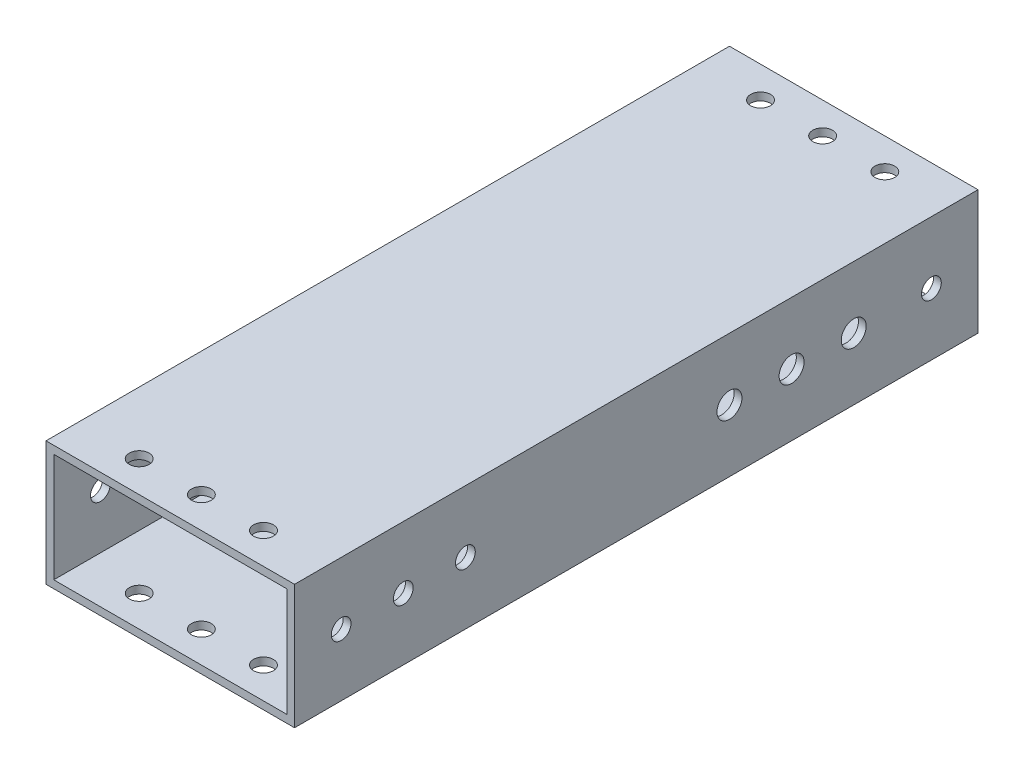
SolidWorks part; units mm, degrees
material "6061-T6 (SS)"
ref_plane "Front Plane" through (0, 0, 0) normal (0, 0, 1) x (1, 0, 0)
ref_plane "Top Plane" through (0, 0, 0) normal (0, 1, 0) x (1, 0, 0)
ref_plane "Right Plane" through (0, 0, 0) normal (1, 0, 0) x (0, 0, -1)
sketch "Sketch1" plane through (0, 0, 0) normal (0, 0, 1) x (1, 0, 0)
  line L0 (-23.8125, 11.1125) -> (23.8125, 11.1125)
  line L1 (-25.4, -12.7) -> (25.4, -12.7)
  line L2 (-25.4, -12.7) -> (-25.4, 12.7)
  line L3 (-25.4, 12.7) -> (25.4, 12.7)
  line L4 (25.4, -12.7) -> (25.4, 12.7)
  line L5 (-25.4, -12.7) -> (25.4, 12.7) construction
  line L6 (-25.4, 12.7) -> (25.4, -12.7) construction
  line L7 (23.8125, -11.1125) -> (23.8125, 11.1125)
  line L8 (-23.8125, -11.1125) -> (23.8125, -11.1125)
  line L9 (-23.8125, -11.1125) -> (-23.8125, 11.1125)
  point P0 (0, 0)
  dimension "D1" = 50.8
  dimension "D2" = 25.4
  dimension "D3" = 1.5875
extrude "Boss-Extrude1" add sketch "Sketch1" along normal mid plane 139.7
sketch "Sketch2" plane through (0, 12.7, 0) normal (0, 1, 0) x (1, 0, 0)
  line L0 (25.4, 69.85) -> (-25.4, 69.85) construction
  line L1 (25.4, 0) -> (-25.4, 0) construction
  line L2 (25.4, -69.85) -> (25.4, 69.85) construction
  line L3 (-25.4, -69.85) -> (-25.4, 69.85) construction
  circle A0 centre (-12.7, 63.5) radius 2.0193
  circle A1 centre (0, 63.5) radius 2.0193
  circle A2 centre (12.7, 63.5) radius 2.0193
  circle A3 centre (12.7, -63.5) radius 2.0193
  circle A4 centre (0, -63.5) radius 2.0193
  circle A5 centre (-12.7, -63.5) radius 2.0193
  dimension "D4" = 4.0386
  dimension "D1" = 12.7
  dimension "D2" = 12.7
  dimension "D3" = 6.35
extrude "Cut-Extrude1" cut sketch "Sketch2" against normal through all
sketch "Sketch3" plane through (-25.4, 0, 0) normal (-1, 0, 0) x (0, 0, 1)
  line L0 (-69.85, 12.7) -> (-69.85, -12.7) construction
  line L1 (0, 12.7) -> (0, -12.7) construction
  line L2 (69.85, 12.7) -> (-69.85, 12.7) construction
  line L3 (69.85, -12.7) -> (-69.85, -12.7) construction
  circle A0 centre (-60.325, 0) radius 2.0193
  circle A1 centre (60.325, 0) radius 2.0193
  circle A4 centre (34.925, 0) radius 2.0193
  circle A5 centre (47.625, 0) radius 2.0193
  dimension "D1" = 4.0386
  dimension "D3" = 12.7
  dimension "D4" = 12.7
  dimension "D2" = 9.525
extrude "Cut-Extrude2" cut sketch "Sketch3" against normal through all contours A5 | A1 | A4 | A0
sketch "Sketch5" plane through (25.4, 0, 0) normal (1, 0, 0) x (0, 0, -1)
  circle A0 centre (31.75, 0) radius 2.5527
  circle A1 centre (44.45, 0) radius 2.5527
  circle A2 centre (19.05, 0) radius 2.5527
  circle A3 centre (60.325, 0) radius 2.0193 construction
  dimension "D1" = 12.7
  dimension "D2" = 12.7
  dimension "D3" = 5.1054
  dimension "D4" = 15.875
extrude "Cut-Extrude3" cut sketch "Sketch5" against normal through all
